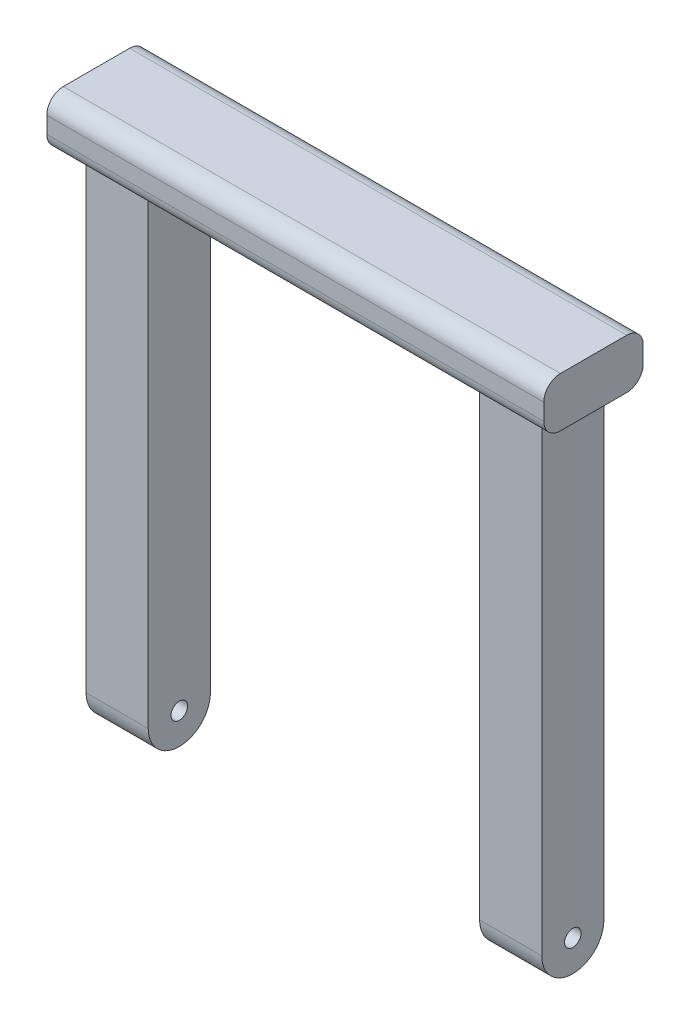
SolidWorks part; units mm, degrees
material "AISI 347 Annealed Stainless Steel (SS)"
ref_plane "Front Plane" through (0, 0, 0) normal (0, 0, 1) x (1, 0, 0)
ref_plane "Top Plane" through (0, 0, 0) normal (0, 1, 0) x (1, 0, 0)
ref_plane "Right Plane" through (0, 0, 0) normal (1, 0, 0) x (0, 0, -1)
sketch "Sketch1" plane through (0, 0, 0) normal (0, 1, 0) x (1, 0, 0)
  line L1 (0, 0) -> (152.4, 0)
  line L2 (0, 0) -> (0, 30.48)
  line L3 (0, 30.48) -> (152.4, 30.48)
  line L4 (152.4, 0) -> (152.4, 30.48)
  dimension "D1" = 30.48
  dimension "D2" = 152.4
extrude "Boss-Extrude1" add sketch "Sketch1" along normal blind 15.24
sketch "Sketch2" plane through (0, 0, 0) normal (0, -1, 0) x (1, 0, 0)
  line L0 (76.2, 0) -> (76.2, -30.48) construction
  line L1 (146.05, -24.765) -> (127, -24.765)
  line L2 (6.35, -5.715) -> (25.4, -5.715)
  line L3 (6.35, -5.715) -> (6.35, -24.765)
  line L12 (6.35, -24.765) -> (25.4, -24.765)
  line L13 (25.4, -5.715) -> (25.4, -24.765)
  line L14 (146.05, -5.715) -> (146.05, -24.765)
  line L15 (146.05, -5.715) -> (127, -5.715)
  line L16 (127, -5.715) -> (127, -24.765)
  dimension "D2" = 19.05
  dimension "D3" = 19.05
  dimension "D5" = 50.8
extrude "Boss-Extrude2" add sketch "Sketch2" along normal blind 152.4
sketch "Sketch3" plane through (6.35, 0, 0) normal (-1, 0, 0) x (0, 0, 1)
  line L4 (-5.715, 0) -> (-24.765, 0)
  line L5 (-24.765, 0) -> (-24.765, -152.4)
  line L6 (-24.765, -152.4) -> (-5.715, -152.4)
  line L7 (-5.715, -152.4) -> (-5.715, 0)
  line L10 (-24.765, -152.4) -> (-5.715, -152.4) construction
  circle A0 centre (-15.24, -142.875) radius 2.54
  dimension "D2" = 5.08
  dimension "D4" = 9.525
  dimension "D1" = 0
extrude "Cut-Extrude1" cut sketch "Sketch3" against normal through all
fillet "Fillet1" radius 9.525 1 edges at (15.875, -152.4, -5.715)
fillet "Fillet2" radius 9.525 1 edges at (15.875, -152.4, -24.765)
fillet "Fillet3" radius 9.525 1 edges at (136.525, -152.4, -24.765)
fillet "Fillet4" radius 9.525 1 edges at (136.525, -152.4, -5.715)
fillet "Fillet5" radius 5.08 1 edges at (76.2, 15.24, 0)
fillet "Fillet6" radius 5.08 1 edges at (76.2, 0, 0)
fillet "Fillet7" radius 5.08 1 edges at (76.2, 0, -30.48)
fillet "Fillet8" radius 5.08 1 edges at (76.2, 15.24, -30.48)
